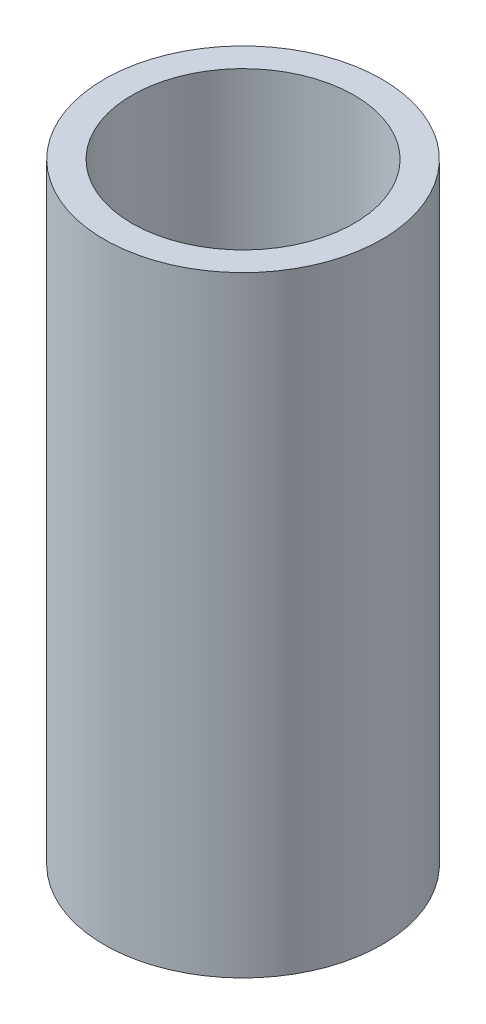
SolidWorks part; units mm, degrees
ref_plane "Płaszczyzna przednia" through (0, 0, 0) normal (0, 0, 1) x (1, 0, 0)
ref_plane "Płaszczyzna górna" through (0, 0, 0) normal (0, 1, 0) x (1, 0, 0)
ref_plane "Płaszczyzna prawa" through (0, 0, 0) normal (1, 0, 0) x (0, 0, -1)
sketch "Sketch1" plane through (0, 0, 0) normal (0, 0, 1) x (1, 0, 0)
  line L0 (0, 0) -> (0, 33) construction
  line L1 (6, 33) -> (0, 33) construction
  line L2 (6, 0) -> (7.5, 0)
  line L3 (6, 0) -> (6, 33)
  line L4 (6, 33) -> (7.5, 33)
  line L5 (7.5, 0) -> (7.5, 33)
  dimension "D1" = 6
  dimension "D2" = 1.5
  dimension "D3" = 33
revolve "Revolve1" add sketch "Sketch1" angle 360 about L0 region at (6.75, 16.5, 0)
